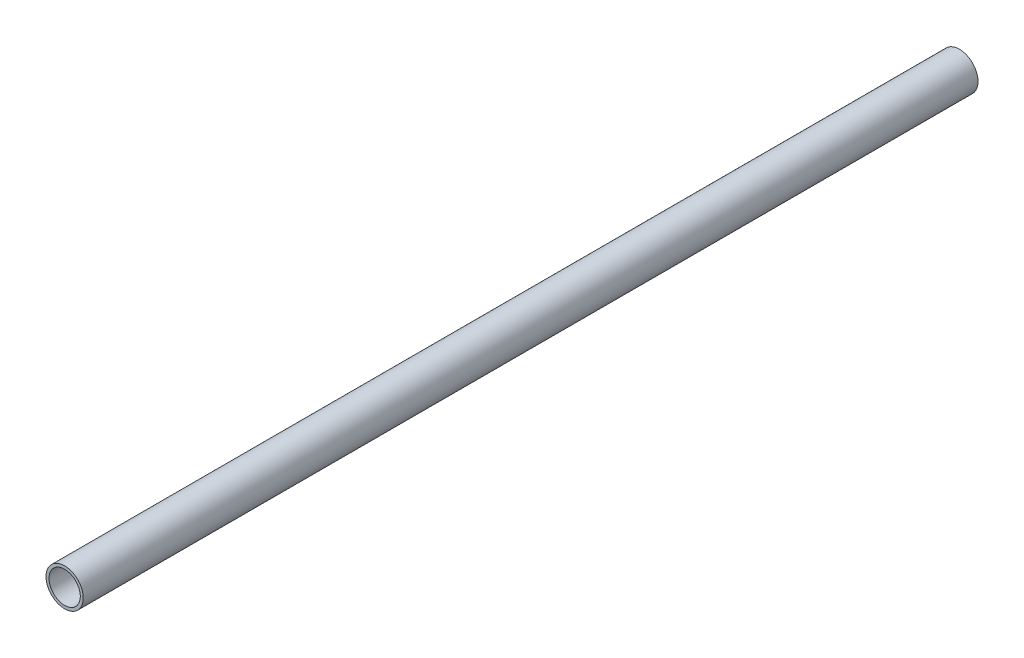
SolidWorks part; units mm, degrees
ref_plane "Front Plane" through (0, 0, 0) normal (0, 0, 1) x (1, 0, 0)
ref_plane "Top Plane" through (0, 0, 0) normal (0, 1, 0) x (1, 0, 0)
ref_plane "Right Plane" through (0, 0, 0) normal (1, 0, 0) x (0, 0, -1)
sketch "Sketch1" plane through (0, 0, 0) normal (0, 0, 1) x (1, 0, 0)
  line L0 (-3.175, 0) -> (3.175, 0) construction
  line L1 (0, 0) -> (0, 1.0456) construction
  point P0 (-2.667, 0)
  point P4 (0, 0)
  point P6 (2.667, 0)
  dimension "OD" = 6.35
  dimension "ID" = 5.334
sketch "Sketch2" plane through (0, 0, 0) normal (0, 0, 1) x (1, 0, 0)
  line L0 (-3.175, 0) -> (3.175, 0) construction
  circle A0 centre (0, 0) radius 2.667
  circle A1 centre (0, 0) radius 3.175
  dimension "D1" = 5.334
  dimension "D2" = 6.35
extrude "Boss-Extrude1" add sketch "Sketch2" along normal mid plane 152.4
sketch "Sketch3" plane through (0, 0, 0) normal (1, 0, 0) x (0, 0, -1)
  line L0 (76.2, 0) -> (-76.2, 0) construction
  line L1 (-76.2, 3.175) -> (-76.2, -3.175) construction
  line L2 (0, 0) -> (0, 21.8825) construction
  point P0 (-75.438, 0)
  point P6 (0, 0)
  point P8 (75.438, 0)
  dimension "D1" = 150.876
ref_axis "Center Axis 1" through (0, 0, 76.2) along (0, 0, -1)
ref_plane "Contact Plane 1" through (0, 0, 76.2) normal (0, 0, 1) x (1, 0, 0)
ref_plane "Contact Plane 2" through (0, 0, -76.2) normal (0, 0, -1) x (-1, 0, 0)
equation "\"D1@Sketch2\"=\"ID@Sketch1\""
equation "\"D2@Sketch2\"=\"OD@Sketch1\""
equation "\"D1@Sketch3\"=\"Length@Boss-Extrude1\"*0.99"
